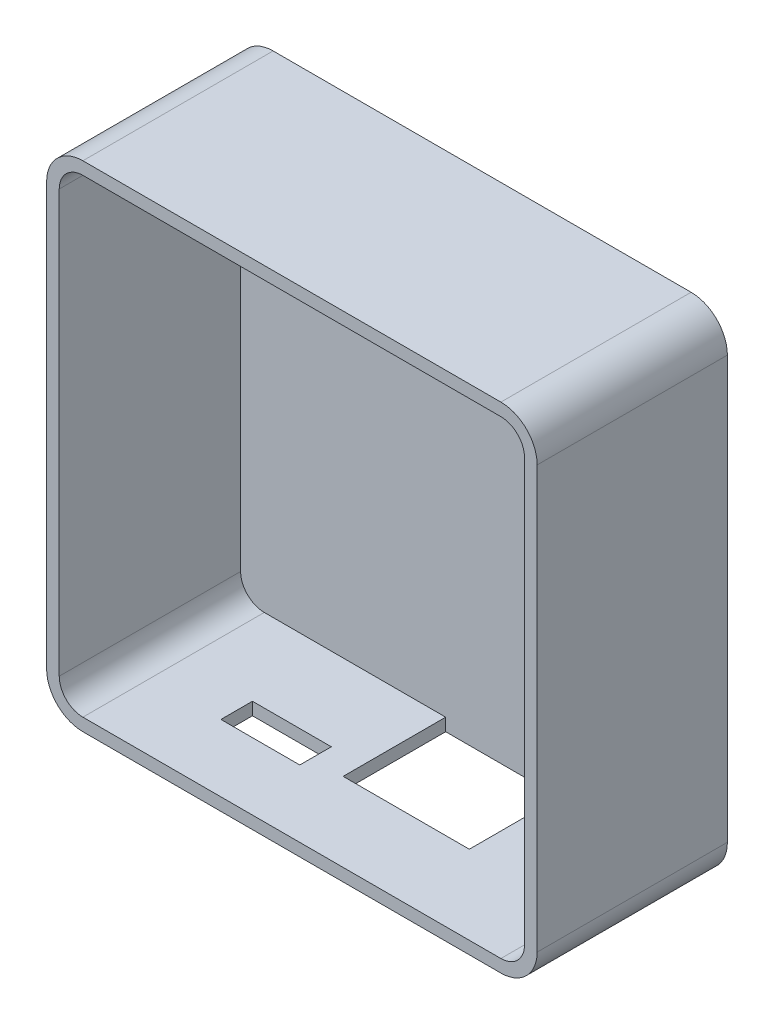
SolidWorks part; units mm, degrees
ref_plane "Alzado" through (0, 0, 0) normal (0, 0, 1) x (1, 0, 0)
ref_plane "Planta" through (0, 0, 0) normal (0, 1, 0) x (1, 0, 0)
ref_plane "Vista lateral" through (0, 0, 0) normal (1, 0, 0) x (0, 0, -1)
sketch "Croquis1" plane through (0, 0, 0) normal (0, 0, 1) x (1, 0, 0)
  line L0 (3, 61.1) -> (56, 61.1)
  line L1 (3, 0) -> (56, 0)
  line L2 (0, 3) -> (0, 56.5)
  line L3 (3, 59.5) -> (56, 59.5)
  line L4 (59, 3) -> (59, 56.5)
  line L5 (60.6, 3) -> (60.6, 56.5)
  line L6 (3, -1.6) -> (56, -1.6)
  line L7 (-1.6, 3) -> (-1.6, 56.5)
  arc A0 (56, 59.5) -> (59, 56.5) centre (56, 56.5) cw
  arc A1 (56, 0) -> (59, 3) centre (56, 3) ccw
  arc A2 (3, 0) -> (0, 3) centre (3, 3) cw
  arc A3 (0, 56.5) -> (3, 59.5) centre (3, 56.5) cw
  arc A4 (56, 61.1) -> (60.6, 56.5) centre (56, 56.5) cw
  arc A5 (56, -1.6) -> (60.6, 3) centre (56, 3) ccw
  arc A6 (3, -1.6) -> (-1.6, 3) centre (3, 3) cw
  arc A7 (-1.6, 56.5) -> (3, 61.1) centre (3, 56.5) cw
  point P9 (59, 0)
  point P12 (0, 0)
  point P15 (0, 59.5)
  dimension "D3" = 3
  dimension "D1" = 59
  dimension "D2" = 59.5
  dimension "D4" = 1.6
extrude "pared" add sketch "Croquis1" along normal blind 23
sketch "Croquis2" plane through (0, -1.6, 0) normal (0, -1, 0) x (1, 0, 0)
  line L0 (0, 23) -> (0, 0) construction
  line L1 (59, 23) -> (59, 0) construction
  line L2 (3, 23) -> (-1.6, 23) construction
  line L3 (-1.6, 23) -> (-1.6, 0) construction
  line L4 (-1.6, 0) -> (3, 0) construction
  line L5 (3, 0) -> (56, 0) construction
  line L6 (56, 0) -> (60.6, 0) construction
  line L7 (60.6, 23) -> (60.6, 0) construction
  line L8 (60.6, 23) -> (56, 23) construction
  line L9 (3, 23) -> (56, 23) construction
  line L10 (0, 23) -> (0, 0)
  line L11 (59, 23) -> (59, 0)
  line L12 (3, 23) -> (-1.6, 23)
  line L13 (-1.6, 23) -> (-1.6, 0)
  line L14 (-1.6, 0) -> (3, 0)
  line L15 (3, 0) -> (56, 0)
  line L16 (56, 0) -> (60.6, 0)
  line L17 (60.6, 23) -> (60.6, 0)
  line L18 (60.6, 23) -> (56, 23)
  line L19 (3, 23) -> (56, 23)
  line L21 (26, 13) -> (42, 13)
  line L22 (26, 13) -> (26, 0)
  line L23 (26, 0) -> (42, 0)
  line L24 (42, 13) -> (42, 0)
  line L25 (12, 14.5) -> (22, 14.5)
  line L26 (12, 14.5) -> (12, 10.5)
  line L27 (12, 10.5) -> (22, 10.5)
  line L28 (22, 14.5) -> (22, 10.5)
  dimension "D1" = 0
  dimension "D2" = 13
  dimension "D3" = 17
  dimension "D4" = 16
  dimension "D5" = 10
  dimension "D6" = 4
  dimension "D7" = 37
  dimension "D8" = 14.5
extrude "conectores" cut sketch "Croquis2" against normal up to next contours L24 L21 L22 L23 | L28 L25 L26 L27 region at (34, -1.6, 6.5) region at (17, -1.6, 12.5)
extrude "base frente" add sketch "Croquis1<2>" against normal blind 1.12 contours A6 L7 A7 L0 A4 L5 A5 L6
sketch "Croquis1<2>" plane through (0, 0, 0) normal (0, 0, 1) x (1, 0, 0) same geometry as "Croquis1"
sketch "Croquis3" plane through (0, 0, 0) normal (0, 0, 1) x (1, 0, 0)
  line L4 (59, 3) -> (59, 56.5)
  line L5 (56, 59.5) -> (3, 59.5)
  line L6 (0, 56.5) -> (0, 3)
  line L7 (3, 0) -> (26, 0)
  line L8 (59, 3) -> (59, 56.5)
  line L9 (56, 59.5) -> (3, 59.5)
  line L10 (0, 56.5) -> (0, 3)
  line L11 (3, 0) -> (26, 0)
  line L24 (54.5, 48) -> (54.5, 41.5) construction
  line L25 (54.5, 28.5) -> (54.5, 17.5) construction
  line L32 (26, 0) -> (26, -1.6)
  line L33 (26, 0) -> (26, -1.6)
  line L34 (26, -1.6) -> (42, -1.6)
  line L35 (26, -1.6) -> (42, -1.6)
  line L36 (42, -1.6) -> (42, 0)
  line L37 (42, -1.6) -> (42, 0)
  line L38 (42, 0) -> (56, 0)
  line L39 (42, 0) -> (56, 0)
  arc A4 (56, 0) -> (59, 3) centre (56, 3) ccw
  arc A5 (59, 56.5) -> (56, 59.5) centre (56, 56.5) ccw
  arc A6 (3, 59.5) -> (0, 56.5) centre (3, 56.5) ccw
  arc A7 (0, 3) -> (3, 0) centre (3, 3) ccw
  arc A8 (56, 0) -> (59, 3) centre (56, 3) ccw
  arc A9 (59, 56.5) -> (56, 59.5) centre (56, 56.5) ccw
  arc A10 (3, 59.5) -> (0, 56.5) centre (3, 56.5) ccw
  circle A16 centre (54.5, 48) radius 1.5
  circle A17 centre (54.5, 41.5) radius 1.5
  circle A18 centre (54.5, 35) radius 1.5
  circle A19 centre (54.5, 28.5) radius 1.5
  circle A20 centre (54.5, 17.5) radius 1.5
  circle A21 centre (54.5, 11.5) radius 2.5
  circle A22 centre (54.5, 48) radius 2.3
  circle A23 centre (54.5, 41.5) radius 2.3
  circle A24 centre (54.5, 35) radius 2.3
  circle A25 centre (54.5, 28.5) radius 2.3
  circle A26 centre (54.5, 17.5) radius 2.3
  circle A27 centre (54.5, 11.5) radius 3.3
  dimension "D14" = 3
  dimension "D3" = 5
  dimension "D2" = 6
  dimension "D4" = 0.8
  dimension "D5" = 4
  dimension "D12" = 6.5
  dimension "D13" = 11.5
  dimension "D15" = 4.5
  dimension "D17" = 11
  dimension "D1" = 0
  dimension "D16" = 2
extrude "luces" cut sketch "Croquis3" against normal up to next contours A16 | A17 | A18 | A19 | A20 | A21 region at (54.5, 48, 0) region at (54.5, 41.5, 0) region at (54.5, 35, 0) region at (54.5, 28.5, 0) region at (54.5, 17.5, 0) region at (54.5, 11.5, 0)
extrude "Saliente-Extruir1" add sketch "Croquis3<3>" along normal blind 12 contours A26 A20 | A25 A19 | A24 A18 | A23 A17 | A22 A16 region at (52.2651, 48, 0) region at (52.2651, 41.5, 0) region at (52.2651, 35, 0) region at (52.2651, 28.5, 0) region at (52.2651, 17.5, 0)
sketch "Croquis3<3>" plane through (0, 0, 0) normal (0, 0, 1) x (1, 0, 0) same geometry as "Croquis3"
extrude "Saliente-Extruir2" add sketch "Croquis3<4>" along normal blind 9 contours A27 A21 region at (51.2933, 11.5, 0)
sketch "Croquis3<4>" plane through (0, 0, 0) normal (0, 0, 1) x (1, 0, 0) same geometry as "Croquis3"
